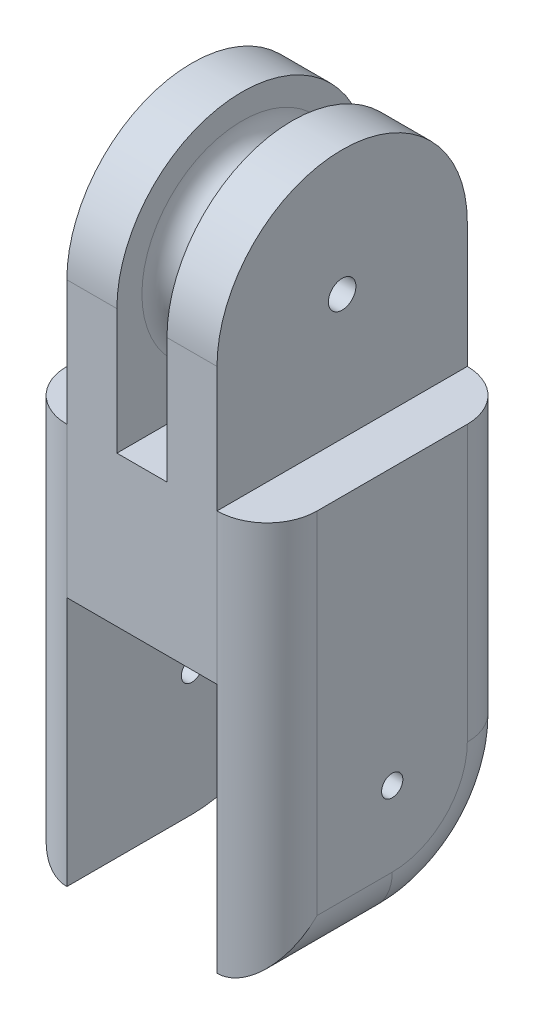
SolidWorks part; units mm, degrees
ref_plane "Front Plane" through (0, 0, 0) normal (0, 0, 1) x (1, 0, 0)
ref_plane "Top Plane" through (0, 0, 0) normal (0, 1, 0) x (1, 0, 0)
ref_plane "Right Plane" through (0, 0, 0) normal (1, 0, 0) x (0, 0, -1)
sketch "Sketch1" plane through (0, 0, 0) normal (0, 1, 0) x (1, 0, 0)
  line L0 (10, 10) -> (-10, -10) construction
  line L1 (-10, 10) -> (10, 10)
  line L2 (-10, 10) -> (-10, -10)
  line L3 (-10, -10) -> (10, -10)
  line L4 (10, 10) -> (10, -10)
  line L5 (-10, 10) -> (10, -10) construction
  point P5 (0, 0)
  dimension "D1" = 20
  dimension "D2" = 20
extrude "Boss-Extrude1" add sketch "Sketch1" along normal blind 12
sketch "Sketch4" plane through (0, 0, 0) normal (0, -1, 0) x (1, 0, 0)
  line L0 (10, -10) -> (-10, -10) construction
  line L1 (-10, 10) -> (-6, 10)
  line L2 (-10, 10) -> (-10, -10)
  line L3 (-10, -10) -> (-6, -10)
  line L4 (-6, 10) -> (-6, -10)
  line L5 (-10, 10) -> (10, 10) construction
  line L6 (10, -10) -> (6, -10)
  line L7 (10, -10) -> (10, 10)
  line L8 (10, 10) -> (6, 10)
  line L9 (6, -10) -> (6, 10)
  dimension "D1" = 4
  dimension "D2" = 4
extrude "Boss-Extrude2" add sketch "Sketch4" along normal blind 10
sketch "Sketch5" plane through (-10, 0, 0) normal (-1, 0, 0) x (0, 0, 1)
  line L0 (10, -10) -> (-10, -10) construction
  line L4 (0, -20) -> (10, -20)
  line L5 (10, -10) -> (10, -20)
  arc A0 (10, -10) -> (0, -20) centre (0, -10) ccw
extrude "Boss-Extrude3" add sketch "Sketch5" against normal blind 4
sketch "Sketch6" plane through (10, 0, 0) normal (1, 0, 0) x (0, 0, -1)
  line L0 (10, -10) -> (-10, -10) construction
  line L4 (0, -20) -> (-10, -20)
  line L5 (-10, -10) -> (-10, -20)
  arc A0 (0, -20) -> (-10, -10) centre (0, -10) ccw
extrude "Boss-Extrude4" add sketch "Sketch6" against normal blind 4
sketch "Sketch7" plane through (-10, 0, 0) normal (-1, 0, 0) x (0, 0, 1)
  circle A0 centre (0, -10) radius 0.85
  dimension "D1" = 1.7
extrude "Cut-Extrude1" cut sketch "Sketch7" against normal through all
fillet "Fillet1" radius 4 8 edges at (-10, -4, 10) (-10, -17.0711, -7.0711) (10, -4, 10) (10, -17.0711, -7.0711) (-10, 1, -10) (10, 1, -10) (10, -20, 5) (-10, -20, 5)
sketch "Sketch8" plane through (0, 12, 0) normal (0, 1, 0) x (1, 0, 0)
  line L0 (6, 10) -> (-6, 10) construction
  line L1 (6, -10) -> (2, -10)
  line L2 (6, -10) -> (6, 10)
  line L3 (6, 10) -> (2, 10)
  line L4 (2, -10) -> (2, 10)
  line L5 (-10, 6) -> (-10, -6) construction
  line L6 (-6, -10) -> (-2, -10)
  line L7 (-6, -10) -> (-6, 10)
  line L8 (-6, 10) -> (-2, 10)
  line L9 (-2, -10) -> (-2, 10)
  line L10 (10, -6) -> (10, 6) construction
  dimension "D1" = 4
  dimension "D2" = 4
  dimension "D3" = 4
  dimension "D4" = 4
extrude "Boss-Extrude5" add sketch "Sketch8" along normal blind 10
sketch "Sketch9" plane through (6, 0, 0) normal (1, 0, 0) x (0, 0, -1)
  line L0 (-10, 22) -> (10, 22) construction
  circle A0 centre (0, 22) radius 10
extrude "Boss-Extrude6" add sketch "Sketch9" against normal blind 4
sketch "Sketch10" plane through (-6, 0, 0) normal (-1, 0, 0) x (0, 0, 1)
  line L0 (-10, 22) -> (10, 22) construction
  circle A0 centre (0, 22) radius 10
extrude "Boss-Extrude7" add sketch "Sketch10" against normal blind 4
sketch "Sketch12" plane through (-6, 0, 0) normal (-1, 0, 0) x (0, 0, 1)
  circle A0 centre (0, 22) radius 1.1
  dimension "D1" = 2.2
extrude "Cut-Extrude2" cut sketch "Sketch12" against normal through all
sketch "Sketch13" plane through (-2, 0, 0) normal (1, 0, 0) x (0, 0, -1)
  circle A0 centre (0, 22) radius 6
  dimension "D1" = 12
sketch "Sketch14" plane through (-2, 0, 0) normal (1, 0, 0) x (0, 0, -1)
  circle A0 centre (0, 22) radius 1.1
  dimension "D1" = 2.2
extrude "Boss-Extrude8" add sketch "Sketch13" along normal blind 4
extrude "Cut-Extrude3" cut sketch "Sketch14" along normal blind 4
fillet "Fillet2" radius 2 2 edges at (2, 22, -6) (-2, 22, 6)
sketch "Sketch16" plane through (0, 0, 0) normal (0, -1, 0) x (1, 0, 0)
  line L0 (6, -10) -> (-6, -10) construction
  line L1 (-6, 0) -> (6, 0) construction
  line L2 (-6, -10) -> (-6, 10) construction
  line L3 (6, 10) -> (6, -10) construction
  circle A0 centre (0, -6) radius 0.5
  circle A1 centre (0, 6) radius 0.5
  dimension "D1" = 1
  dimension "D2" = 4
extrude "Cut-Extrude4" cut sketch "Sketch16" against normal up to next
